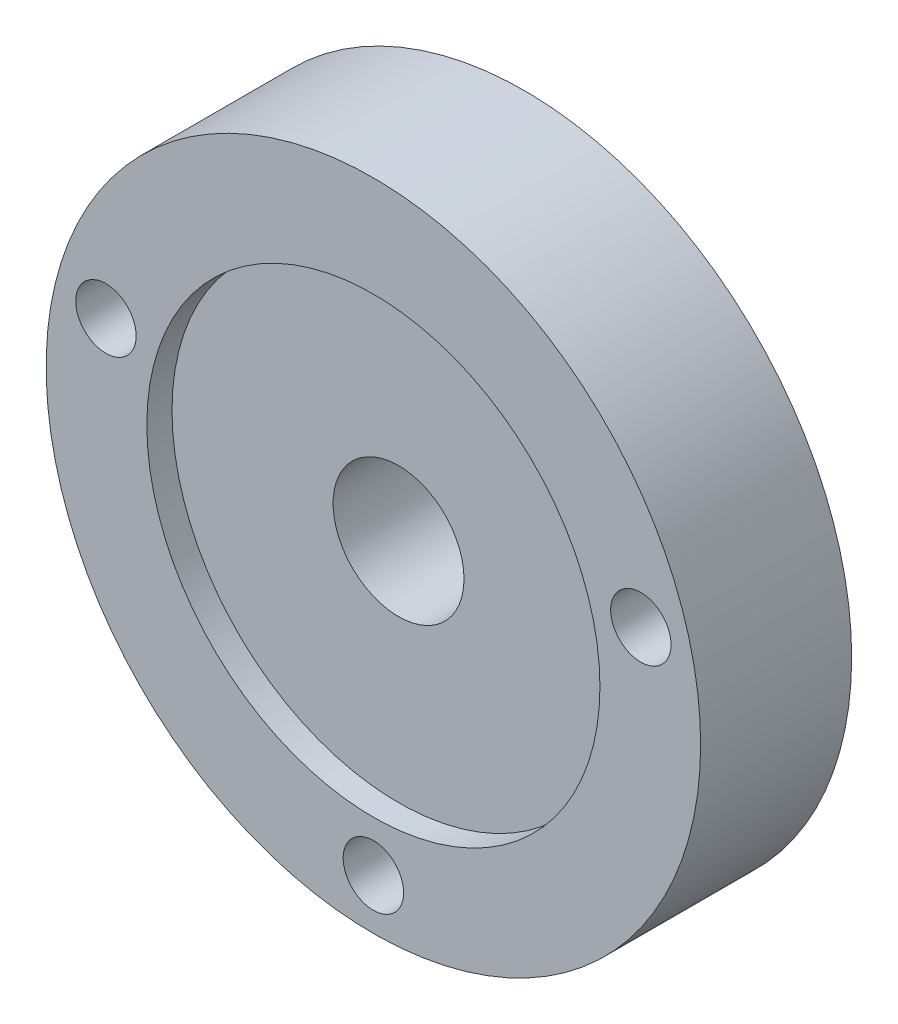
SolidWorks part; units mm, degrees
ref_plane "Plan de face" through (0, 0, 0) normal (0, 0, 1) x (1, 0, 0)
ref_plane "Plan de dessus" through (0, 0, 0) normal (0, 1, 0) x (1, 0, 0)
ref_plane "Plan de droite" through (0, 0, 0) normal (1, 0, 0) x (0, 0, -1)
sketch "Esquisse1" plane through (0, 0, 0) normal (0, 0, 1) x (1, 0, 0)
  circle A0 centre (0, 0) radius 32.5
  dimension "D1" = 65
extrude "Boss.-Extru.1" add sketch "Esquisse1" along normal blind 15
sketch "Esquisse2" plane through (0, 0, 15) normal (0, 0, 1) x (1, 0, 0)
  circle A0 centre (0, 0) radius 22.5
  dimension "D1" = 45
extrude "Enlèv. mat.-Extru.1" cut sketch "Esquisse2" against normal blind 2.5
sketch "Esquisse3" plane through (0, 0, 12.5) normal (0, 0, 1) x (1, 0, 0)
  circle A0 centre (0, 0) radius 6.5
  dimension "D1" = 13
extrude "Enlèv. mat.-Extru.2" cut sketch "Esquisse3" against normal through all
hole_wizard "Trous de centrage Ø6.0mm1" positions "Esquisse5" profile "Esquisse4" hole size "Ø6.0" standard "ISO" end condition through all
sketch "Esquisse5" plane through (0, 0, 15) normal (0, 0, 1) x (1, 0, 0)
  point P0 (0, -27.5)
  point P2 (-26.563, 7.1175)
  point P4 (26.563, 7.1175)
sketch "Esquisse4" plane through (0, -27.5, 15) normal (1, 0, 0) x (0, -1, 0)
  line L0 (0, 0) -> (0, 15)
  line L1 (0, 15) -> (3, 15)
  line L2 (3, 15) -> (3, 0)
  line L5 (3, 0) -> (0, 0)
  line L11 (0, -6.35) -> (0, 107.95) construction
  dimension "Diamètre du perçage jusqu'au prochain" = 6
  dimension "Profondeur du perçage jusqu'au prochain" = 15
ref_axis "Axe1" through (0, 0, 15) along (0, 0, -1)
hole_wizard "Dégagement M61" positions "Esquisse9" profile "Esquisse10" hole size "M6" standard "JIS"
sketch "Esquisse9" plane through (0, 0, 0) normal (0, 0, -1) x (-1, 0, 0)
  point P0 (-11.3038, 11.241)
  point P2 (9.1074, 13.084)
  point P4 (14.4667, -6.697)
sketch "Esquisse10" plane through (11.3038, 11.241, 0) normal (1, 0, 0) x (0, 1, 0)
  line L0 (0, 0) -> (0, 6.9053)
  line L1 (0, 6.9053) -> (3.3, 5)
  line L2 (3.3, 5) -> (3.3, 0)
  line L5 (3.3, 0) -> (0, 0)
  line L10 (0, 6.9053) -> (-3.3, 5) construction
  line L11 (0, -6.35) -> (0, 107.95) construction
  dimension "Diamètre du perçage" = 6.6
  dimension "Profondeur du perçage" = 5
  dimension "Angle de pointe" = 120
hole_wizard "Dégagement M31" positions "Esquisse13" profile "Esquisse11" hole size "M3" standard "JIS"
sketch "Esquisse13" plane through (0, 0, 0) normal (0, 0, -1) x (-1, 0, 0)
  point P0 (22.2986, -9.3881)
  point P2 (21.9062, 10.6081)
sketch "Esquisse11" plane through (-22.2986, -9.3881, 0) normal (1, 0, 0) x (0, 1, 0)
  line L0 (0, 0) -> (0, 5.9815)
  line L1 (0, 5.9815) -> (1.7, 5)
  line L2 (1.7, 5) -> (1.7, 0)
  line L5 (1.7, 0) -> (0, 0)
  line L10 (0, 5.9815) -> (-1.7, 5) construction
  line L11 (0, -6.35) -> (0, 107.95) construction
  dimension "Diamètre du perçage" = 3.4
  dimension "Profondeur du perçage" = 5
  dimension "Angle de pointe" = 120
hole_wizard "Dégagement M32" positions "Esquisse15" profile "Esquisse14" hole size "M3" standard "JIS"
sketch "Esquisse15" plane through (0, 0, 0) normal (0, 0, -1) x (-1, 0, 0)
  point P0 (-21.9238, -9.7082)
  point P2 (-22.2986, 9.3881)
sketch "Esquisse14" plane through (21.9238, -9.7082, 0) normal (1, 0, 0) x (0, 1, 0)
  line L0 (0, 0) -> (0, 5.9815)
  line L1 (0, 5.9815) -> (1.7, 5)
  line L2 (1.7, 5) -> (1.7, 0)
  line L5 (1.7, 0) -> (0, 0)
  line L10 (0, 5.9815) -> (-1.7, 5) construction
  line L11 (0, -6.35) -> (0, 107.95) construction
  dimension "Diamètre du perçage" = 3.4
  dimension "Profondeur du perçage" = 5
  dimension "Angle de pointe" = 120
